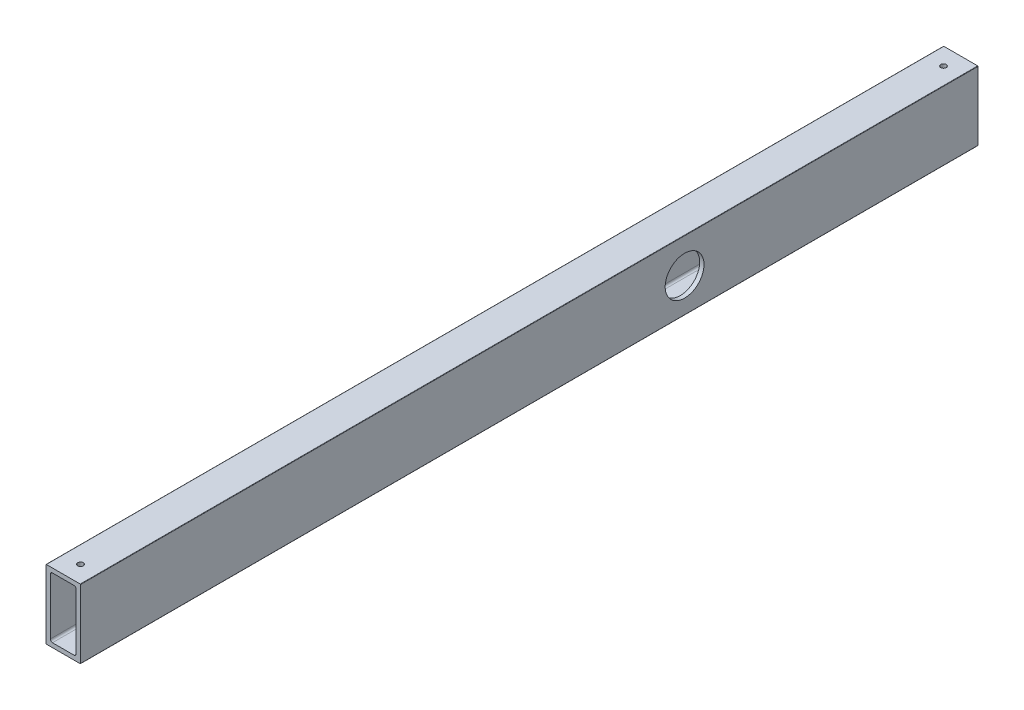
SolidWorks part; units mm, degrees
material "3.0205 (EN-AW 1200)"
ref_plane "Front Plane" through (0, 0, 0) normal (0, 0, 1) x (1, 0, 0)
ref_plane "Top Plane" through (0, 0, 0) normal (0, 1, 0) x (1, 0, 0)
ref_plane "Right Plane" through (0, 0, 0) normal (1, 0, 0) x (0, 0, -1)
ref_plane "Plane1" through (0, 0, 0) normal (0, 0, -1) x (-1, 0, 0)
sketch "Sketch1" plane through (0, 0, 0) normal (0, 0, -1) x (-1, 0, 0)
  line L0 (-3.175, 46.0375) -> (-3.175, 4.7625)
  line L1 (-4.7625, 3.175) -> (-20.6375, 3.175)
  line L2 (-22.225, 4.7625) -> (-22.225, 46.0375)
  line L3 (-20.6375, 47.625) -> (-4.7625, 47.625)
  line L4 (0, 0.254) -> (0, 50.546)
  line L5 (-0.254, 50.8) -> (-25.146, 50.8)
  line L6 (-25.4, 50.546) -> (-25.4, 0.254)
  line L7 (-25.146, 0) -> (-0.254, 0)
  arc A0 (-3.175, 4.7625) -> (-4.7625, 3.175) centre (-4.7625, 4.7625) cw
  arc A1 (-20.6375, 3.175) -> (-22.225, 4.7625) centre (-20.6375, 4.7625) cw
  arc A2 (-22.225, 46.0375) -> (-20.6375, 47.625) centre (-20.6375, 46.0375) cw
  arc A3 (-4.7625, 47.625) -> (-3.175, 46.0375) centre (-4.7625, 46.0375) cw
  arc A4 (-0.254, 0) -> (0, 0.254) centre (-0.254, 0.254) ccw
  arc A5 (0, 50.546) -> (-0.254, 50.8) centre (-0.254, 50.546) ccw
  arc A6 (-25.146, 50.8) -> (-25.4, 50.546) centre (-25.146, 50.546) ccw
  arc A7 (-25.4, 0.254) -> (-25.146, 0) centre (-25.146, 0.254) ccw
extrude "Boss-Extrude1" add sketch "Sketch1" against normal blind 660.4
sketch "Sketch2" plane through (0, 50.8, 0) normal (0, 1, 0) x (1, 0, 0)
  line L0 (0.254, -660.4) -> (25.146, -660.4) construction
  line L1 (25.146, -330.2) -> (0, -330.2) construction
  line L2 (25.146, -660.4) -> (25.146, 0) construction
  line L3 (0, -660.4) -> (0, 0) construction
  circle A0 centre (12.7, -647.7) radius 2.032
  circle A1 centre (12.7, -673.1) radius 2.032
  circle A2 centre (12.7, 12.7) radius 2.032
  circle A3 centre (12.7, -12.7) radius 2.032
  dimension "D1" = 4.064
  dimension "D2" = 4.064
  dimension "D3" = 12.7
  dimension "D4" = 25.4
extrude "Cut-Extrude1" cut sketch "Sketch2" against normal through all
sketch "Sketch5" plane through (25.4, 0, 0) normal (1, 0, 0) x (0, 0, -1)
  line L0 (-660.4, 50.546) -> (0, 50.546) construction
  line L2 (0, 50.546) -> (0, 0.254) construction
  circle A0 centre (-215.9, 25.146) radius 14.2875
  dimension "D1" = 28.575
  dimension "D2" = 25.4
  dimension "D3" = 215.9
extrude "Cut-Extrude2" cut sketch "Sketch5" against normal through all
